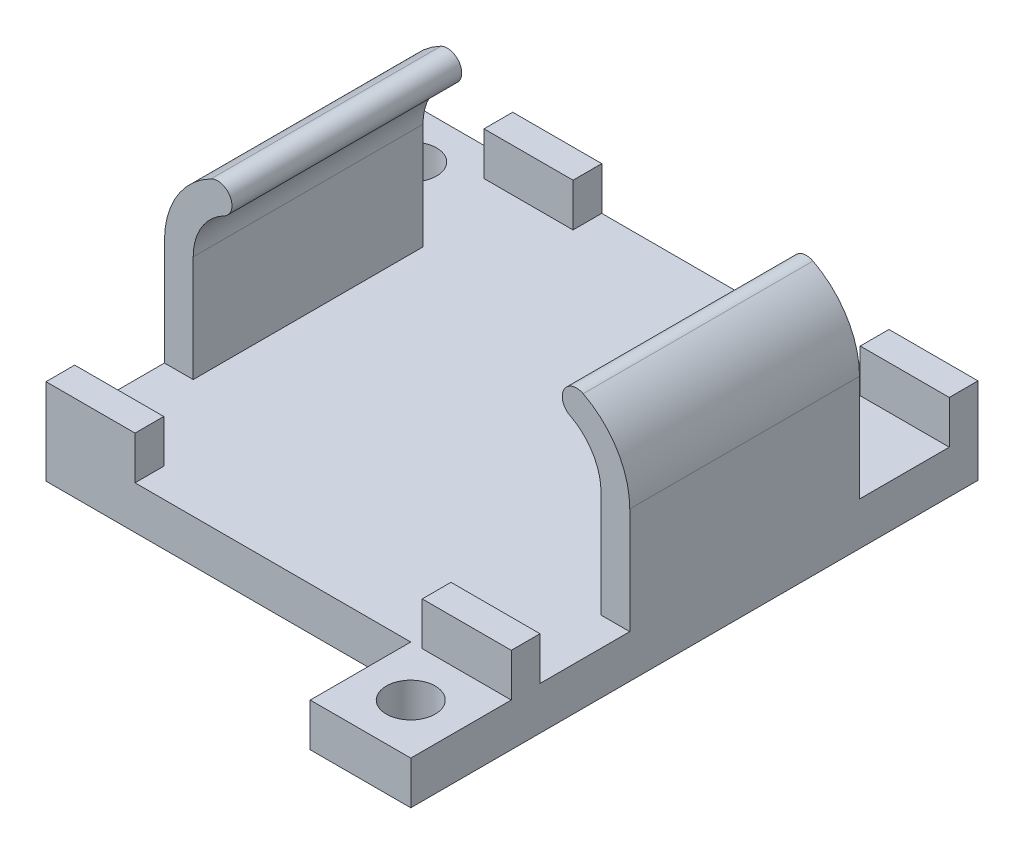
SolidWorks part; units mm, degrees
ref_plane "Front Plane" through (0, 0, 0) normal (0, 0, 1) x (1, 0, 0)
ref_plane "Top Plane" through (0, 0, 0) normal (0, 1, 0) x (1, 0, 0)
ref_plane "Right Plane" through (0, 0, 0) normal (1, 0, 0) x (0, 0, -1)
sketch "Sketch1" plane through (0, 0, 0) normal (0, 0, 1) x (1, 0, 0)
  line L0 (-16.2, -2.2) -> (16.2, -2.2)
  line L1 (-10.2, 8.2) -> (10.2, 8.2)
  line L2 (-16.2, 2.2) -> (-16.2, -8.2)
  line L3 (-16.2, -8.2) -> (16.2, -8.2)
  line L4 (16.2, 2.2) -> (16.2, -8.2)
  line L5 (-16.2, 8.2) -> (16.2, -8.2) construction
  line L6 (-16.2, -8.2) -> (16.2, 8.2) construction
  line L7 (-10.2, 6.2) -> (10.2, 6.2)
  line L8 (-14.2, 2.2) -> (-14.2, -5.2)
  line L9 (-14.2, -5.2) -> (14.2, -5.2)
  line L10 (14.2, 2.2) -> (14.2, -5.2)
  line L11 (-16.2, -5.2) -> (16.2, -5.2)
  line L17 (-10, 4) -> (10, 4)
  line L18 (-10, 4) -> (-10, -5.2)
  line L19 (-10, -5.2) -> (10, -5.2)
  line L20 (10, 4) -> (10, -5.2)
  arc A0 (14.2, 2.2) -> (10.2, 6.2) centre (10.2, 2.2) ccw
  arc A1 (-14.2, 2.2) -> (-10.2, 6.2) centre (-10.2, 2.2) cw
  arc A2 (16.2, 2.2) -> (10.2, 8.2) centre (10.2, 2.2) ccw
  arc A3 (-16.2, 2.2) -> (-10.2, 8.2) centre (-10.2, 2.2) cw
  circle A4 centre (-12.5, 6.6396) radius 1
  circle A5 centre (12.5, 6.6396) radius 1
  point P0 (0, 0)
  point P10 (0, -5.2)
  point P15 (-14.2, 6.2)
  point P30 (0, 0)
  point P35 (0, 4)
  dimension "D5" = 4
  dimension "D6" = 6
  dimension "D9" = 12.5
  dimension "D1" = 11.4
  dimension "D2" = 3
  dimension "D3" = 2
  dimension "D4" = 28.4
  dimension "D7" = 2
  dimension "D8" = 12.5
  dimension "D10" = 4
  dimension "D11" = 20
  dimension "D12" = 3
extrude "Boss-Extrude1" add sketch "Sketch1" along normal blind 14.25 and the other way blind 14.25 contours L11 L2 L3 L4 L9 region at (0, -6.7, 0)
extrude "Boss-Extrude2" add sketch "Sketch1<3>" along normal blind 2 from surface contours L11 L2 L3 L4 L9 | L2 L11 L8 L0 | L18 L0 L8 L9 | L0 L20 L9 L10 | L10 L11 L4 L0 region at (-15.2, -3.7, 0) region at (-12.1, -3.7, 0) region at (0, -6.7, 0) region at (12.1, -3.7, 0) region at (15.2, -3.7, 0) starting at face at (0, -6.7, 14.25)
sketch "Sketch1<3>" plane through (0, 0, 0) normal (0, 0, 1) x (1, 0, 0) same geometry as "Sketch1"
extrude "Boss-Extrude3" add sketch "Sketch1<6>" against normal blind 2 from surface contours L2 L11 L8 L0 | L18 L0 L8 L9 | L11 L2 L3 L4 L9 | L0 L20 L9 L10 | L10 L11 L4 L0 region at (-15.2, -3.7, 0) region at (-12.1, -3.7, 0) region at (0, -6.7, 0) region at (12.1, -3.7, 0) region at (15.2, -3.7, 0) starting at face at (0, -6.7, -14.25)
sketch "Sketch1<6>" plane through (0, 0, 0) normal (0, 0, 1) x (1, 0, 0) same geometry as "Sketch1"
extrude "Boss-Extrude4" add sketch "Sketch1<7>" along normal blind 8 and the other way blind 8 contours L2 L11 L8 L0 | A4 A3 L2 L0 L8 A1 | A4 | A5 | A5 A0 L10 L0 L4 A2 | L10 L11 L4 L0 region at (-14.8694, 2.2734, 0) region at (-15.2, -3.7, 0) region at (-12.5, 6.6396, 0) region at (14.8694, 2.2734, 0) region at (15.2, -3.7, 0) region at (12.5, 6.6396, 0)
sketch "Sketch1<7>" plane through (0, 0, 0) normal (0, 0, 1) x (1, 0, 0) same geometry as "Sketch1"
sketch "Sketch2" plane through (0, 0, 0) normal (0, 1, 0) x (1, 0, 0)
  line L1 (-23.2, 16.25) -> (-16.2, 16.25)
  line L2 (-23.2, 16.25) -> (-23.2, 9.25)
  line L3 (-23.2, 9.25) -> (-16.2, 9.25)
  line L4 (-16.2, 16.25) -> (-16.2, 9.25)
  line L5 (9.2, -16.25) -> (16.2, -16.25)
  line L6 (9.2, -16.25) -> (9.2, -23.25)
  line L7 (9.2, -23.25) -> (16.2, -23.25)
  line L8 (16.2, -16.25) -> (16.2, -23.25)
  line L9 (-16.2, 14.25) -> (-16.2, 8) construction
  line L11 (-10, 16.25) -> (10, 16.25) construction
  line L13 (10, -16.25) -> (-10, -16.25) construction
  line L14 (16.2, 14.25) -> (16.2, 8) construction
  circle A0 centre (-19.7, 12.75) radius 1.7
  circle A1 centre (12.7, -19.75) radius 1.7
  point P13 (16.2, -19.75)
  point P17 (-23.2, 12.75)
  dimension "D7" = 3.4
  dimension "D8" = 3.4
  dimension "D1" = 7
  dimension "D2" = 7
  dimension "D3" = 7
  dimension "D4" = 7
  dimension "D5" = 3.5
  dimension "D6" = 3.5
extrude "Boss-Extrude5" add sketch "Sketch2" along normal blind 3 from surface starting at face at (0, -8.2, 0)
sketch "Sketch3" plane through (0, 0, 0) normal (0, 1, 0) x (1, 0, 0)
  line L1 (-19.7, 12.75) -> (12.7, 12.75)
  line L2 (-19.7, 12.75) -> (-19.7, -19.75)
  line L3 (-19.7, -19.75) -> (12.7, -19.75)
  line L4 (12.7, 12.75) -> (12.7, -19.75)
  line L5 (-19.7, 12.75) -> (12.7, -19.75) construction
  line L6 (-19.7, -19.75) -> (12.7, 12.75) construction
  circle A0 centre (-19.7, 12.75) radius 1.7 construction
  circle A1 centre (12.7, -19.75) radius 1.7 construction
